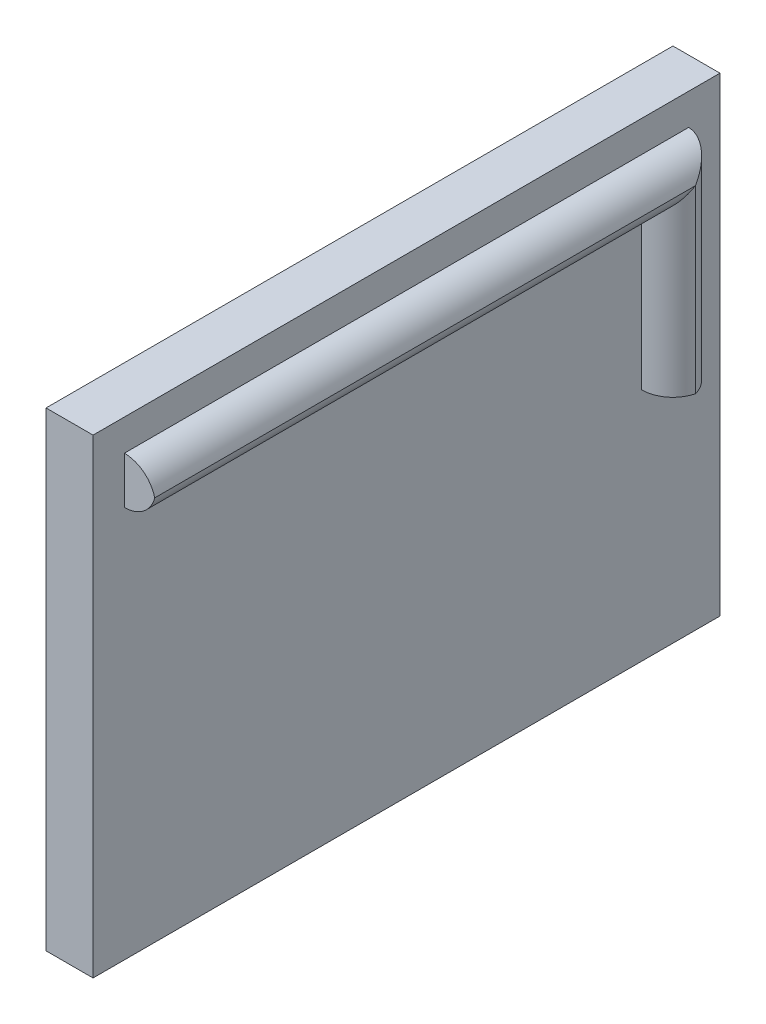
SolidWorks part; units mm, degrees
ref_plane "Front Plane" through (0, 0, 0) normal (0, 0, 1) x (1, 0, 0)
ref_plane "Top Plane" through (0, 0, 0) normal (0, 1, 0) x (1, 0, 0)
ref_plane "Right Plane" through (0, 0, 0) normal (1, 0, 0) x (0, 0, -1)
sketch "Sketch1" plane through (0, 0, 0) normal (1, 0, 0) x (0, 0, -1)
  line L1 (-20, 15) -> (20, 15)
  line L2 (-20, 15) -> (-20, -15)
  line L3 (-20, -15) -> (20, -15)
  line L4 (20, 15) -> (20, -15)
  line L5 (-20, 15) -> (20, -15) construction
  line L6 (-20, -15) -> (20, 15) construction
  point P0 (0, 0)
  dimension "D1" = 40
  dimension "D2" = 30
extrude "Boss-Extrude1" add sketch "Sketch1" along normal blind 3
sketch "Sketch2" plane through (3, 0, 0) normal (1, 0, 0) x (0, 0, -1)
  line L0 (20, -15) -> (20, 15) construction
  line L1 (18, 13) -> (-18, 13)
  line L3 (15, 10) -> (-15, 10)
  line L4 (-18, 13) -> (-18, 10)
  line L5 (-20, 15) -> (-20, -15) construction
  line L7 (-18, 13) -> (-13.7685, 13)
  line L8 (-18, 13) -> (-18, 10)
  line L11 (18, 13) -> (18, 0)
  line L12 (18, 0) -> (15, 0)
  line L13 (15, 0) -> (15, 10)
  line L14 (-15, 10) -> (-18, 10)
  dimension "D3" = 2
  dimension "D4" = 2
  dimension "D5" = 3
extrude "Boss-Extrude2" add sketch "Sketch2" along normal blind 2
fillet "Fillet1" radius 2 4 edges at (5, 10, 1.5) (5, 13, 0) (5, 5, -15) (5, 6.5, -18)
